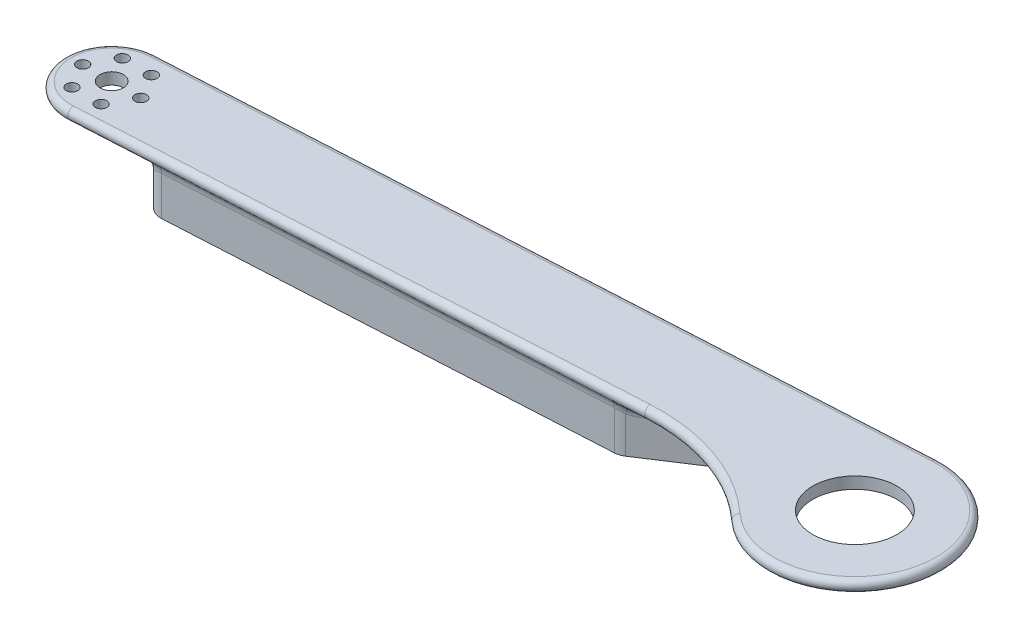
SolidWorks part; units mm, degrees
material "ABS"
ref_plane "Front Plane" through (0, 0, 0) normal (0, 0, 1) x (1, 0, 0)
ref_plane "Top Plane" through (0, 0, 0) normal (0, 1, 0) x (1, 0, 0)
ref_plane "Right Plane" through (0, 0, 0) normal (1, 0, 0) x (0, 0, -1)
ref_axis "Axis1" through (0, 55, 0) along (0, -1, 0)
sketch "Sketch2" plane through (0, 0, 0) normal (0, 1, 0) x (1, 0, 0)
  line L0 (-203.8945, 12.681) -> (-1.3022, 23.7769)
  line L1 (-1.3022, 23.7769) -> (0, 0) construction
  line L2 (-203.8945, 12.681) -> (-202.5055, -12.681) construction
  line L3 (-202.5055, -12.681) -> (-52.9616, -4.4906)
  circle A0 centre (-203.2, 0) radius 12.7 construction
  circle A1 centre (0, 0) radius 23.8125 construction
  circle A2 centre (-0.6077, 11.0959) radius 12.7 construction
  arc A3 (-203.8945, 12.681) -> (-202.5055, -12.681) centre (-203.2, 0) ccw
  arc A5 (-1.3022, 23.7769) -> (-16.016, -17.6217) centre (0, 0) cw
  circle A6 centre (0, 0) radius 11.5
  arc A7 (-52.9616, -4.4906) -> (-16.016, -17.6217) centre (-50.1835, -55.2145) cw
  dimension "D1" = 25.4
  dimension "D2" = 47.625
  dimension "D3" = 23
  dimension "D4" = 50.8
extrude "Boss-Extrude1" add sketch "Sketch2" along normal mid plane 3.175
sketch "Sketch5" plane through (0, 0, 0) normal (0, 1, 0) x (1, 0, 0)
  line L0 (0, 0) -> (0, 15.875) construction
  circle A0 centre (0, 15.875) radius 1.5875
  dimension "D1" = 3.175
  dimension "D2" = 15.875
extrude "Cut-Extrude3" [suppressed] cut sketch "Sketch5" against normal through all both and the other way through all
pattern_circular "CirPattern1" [suppressed] count 8 over 360 about axis through (0, 55, 0) along (0, -1, 0) of bodies 104
sketch "Sketch3" plane through (0, 0, 0) normal (0, 1, 0) x (1, 0, 0)
  line L0 (-34.1312, 0) -> (-23.8125, 0) construction
  line L2 (-190.5, 0) -> (-180.1812, 0) construction
  circle A1 centre (-34.1312, 0) radius 1.5875
  circle A2 centre (-180.1812, 0) radius 1.5875
  circle A3 centre (-165.5762, 0) radius 1.5875
  circle A4 centre (-150.9712, 0) radius 1.5875
  circle A5 centre (-136.3662, 0) radius 1.5875
  circle A6 centre (-121.7612, 0) radius 1.5875
  circle A7 centre (-107.1562, 0) radius 1.5875
  circle A8 centre (-92.5512, 0) radius 1.5875
  circle A9 centre (-77.9462, 0) radius 1.5875
  circle A10 centre (-63.3412, 0) radius 1.5875
  circle A11 centre (-48.7362, 0) radius 1.5875
  arc A12 (-203.8945, 12.681) -> (-202.5055, -12.681) centre (-203.2, 0) ccw construction
  arc A14 (-16.016, -17.6217) -> (-1.3022, 23.7769) centre (0, 0) ccw construction
  dimension "D2" = 3.175
  dimension "D1" = 146.05
  dimension "D3" = 11
extrude "Cut-Extrude1" [suppressed] cut sketch "Sketch3" against normal through all both and the other way through all
sketch "Sketch4" plane through (0, 0, 0) normal (0, -1, 0) x (1, 0, 0)
  line L0 (-203.2, 0) -> (-195.2625, 0) construction
  circle A0 centre (-203.2, 0) radius 3.175
  circle A1 centre (-195.2625, 0) radius 1.5875
  dimension "D1" = 6.35
  dimension "D2" = 3.175
  dimension "D3" = 7.9375
extrude "Cut-Extrude2" cut sketch "Sketch4" against normal through all both and the other way through all
pattern_circular "CirPattern2" count 6 over 360 about axis through (-203.2, 1.5875, 0) along (0, -1, 0) of "Cut-Extrude2" reverse direction yes
fillet "Fillet1" 2 edges at (22.4375, 1.5875, 7.9747) (22.4375, -1.5875, 7.9747) type full round first side face at (-211.1375, 1.5875, 1.5875) second side face at (-211.1375, -1.5875, 1.5875) middle face at (6.8892, 0, 2.4485)
sketch "Sketch6" plane through (0, -1.5875, 0) normal (0, -1, 0) x (-1, 0, 0)
  line L0 (31.7025, -1.7363) -> (32.9179, 20.4554) construction
  line L1 (31.7025, -1.7363) -> (187.1424, -10.2497) construction
  line L2 (32.9179, 20.4554) -> (188.3578, 11.9421)
  line L3 (187.1424, -10.2497) -> (188.3578, 11.9421) construction
  line L4 (31.7025, -1.7363) -> (188.3578, 11.9421) construction
  line L5 (32.9179, 20.4554) -> (187.1424, -10.2497) construction
  line L6 (203.8077, 11.0959) -> (1.2154, 22.1917) construction
  line L7 (53.0484, -2.9054) -> (202.5923, -11.0959) construction
  line L8 (23.8555, 20.9518) -> (32.9179, 20.4554)
  line L9 (187.1424, -10.2497) -> (61.0773, -3.3452)
  line L10 (61.0773, -3.3452) -> (23.8555, 20.9518)
  arc A1 (23.8555, 20.9518) -> (31.7025, -1.7363) centre (0, 0) cw construction
  arc A2 (188.3578, 11.9421) -> (187.1424, -10.2497) centre (203.2, 0) ccw
  point P1 (110.0302, 5.1029)
  dimension "D2" = 31.75
  dimension "D1" = 19.05
  dimension "D3" = 30
extrude "Boss-Extrude2" add sketch "Sketch6" along normal blind 12.7
fillet "Fillet2" radius 4.7625 4 edges at (-188.3578, -7.9375, -11.9421) (-23.8555, -7.9375, -20.9518) (-61.0773, -7.9375, 3.3452) (-187.1424, -7.9375, 10.2497)
fillet "Fillet3" radius 3.175 8 edges at (-183.5636, -1.5875, 8.1722) (-121.014, -1.5875, 6.6279) (-61.1296, -1.5875, 3.1855) (-49.3739, -1.5875, -4.2943) (-36.8164, -1.5875, -16.7067) (-111.2473, -1.5875, -16.1654) (-184.5735, -1.5875, -10.2678) (-184.1785, -1.5875, -1.0418)
